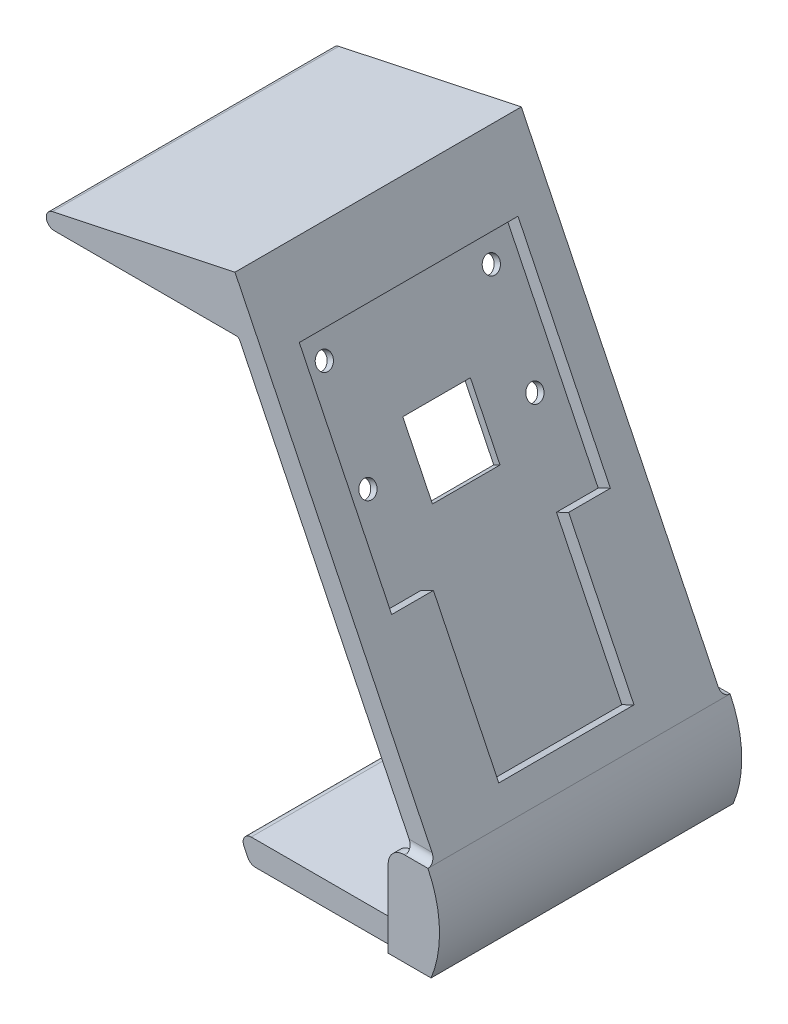
SolidWorks part; units mm, degrees
ref_plane "Front Plane" through (0, 0, 0) normal (0, 0, 1) x (1, 0, 0)
ref_plane "Top Plane" through (0, 0, 0) normal (0, 1, 0) x (1, 0, 0)
ref_plane "Right Plane" through (0, 0, 0) normal (1, 0, 0) x (0, 0, -1)
sketch "Sketch2" plane through (0, 0, 0) normal (0, 0, 1) x (1, 0, 0)
  line L0 (0, 0) -> (-25.1844, 51.6357)
  line L1 (0, 0) -> (-52.1043, 0) construction
  line L2 (0, 0) -> (0, -2)
  line L3 (0, -2) -> (-23.62, -2)
  line L6 (-25.1844, 51.6357) -> (-48.3844, 51.6357)
  line L7 (-48.5923, 53.6139) -> (-25.6548, 58.4894)
  line L8 (-25.6548, 58.4894) -> (-0.3927, 6.6946)
  line L10 (-24.04, -4.4528) -> (-24.5278, -3.4528)
  line L11 (0, -5.0472) -> (-23.13, -5.0472)
  arc A0 (-48.5923, 53.6139) -> (-48.3844, 51.6357) centre (-48.3844, 52.6357) ccw
  arc A1 (-23.62, -2) -> (-24.5278, -3.4528) centre (-23.62, -3.01) ccw
  arc A3 (-24.04, -4.4528) -> (-23.13, -5.0472) centre (-23.0873, -3.9881) ccw
  arc A4 (-0.3927, 6.6946) -> (0, -5.0472) centre (-13.3306, 0.3843) cw
  point P17 (-13.3306, 0.3843)
  dimension "D6" = 1
  dimension "D12" = 1.01
  dimension "D8" = 1.06
  dimension "D1" = 64
  dimension "D2" = 57.45
  dimension "D3" = 23.2
  dimension "D4" = 23.45
  dimension "D5" = 12
  dimension "D7" = 23.62
  dimension "D9" = 2
  dimension "D10" = 1
  dimension "D11" = 64
  dimension "D14" = 23.13
extrude "Boss-Extrude1" add sketch "Sketch2" along normal blind 36 contours L6 A0 L7 L8 A4 L11 A3 L10 A1 L3 L2 L0
sketch "Sketch4" plane through (2.3204, 1.1317, 0) normal (0.8988, 0.4384, 0) x (0, 0, -1)
  line L0 (-18, 53.8162) -> (-18, 29.8162) construction
  line L1 (-30.5, 29.8162) -> (-5.5, 29.8162)
  line L2 (-30.5, 29.8162) -> (-30.5, 53.8162)
  line L3 (-30.5, 53.8162) -> (-5.5, 53.8162)
  line L4 (-5.5, 29.8162) -> (-5.5, 53.8162)
  line L5 (-28.5, 53.8162) -> (-28.5, 29.8162) construction
  line L6 (-7.5, 29.8162) -> (-7.5, 53.8162) construction
  line L7 (-30.5, 51.8162) -> (-5.5, 51.8162) construction
  line L8 (-30.5, 39.3162) -> (-5.5, 39.3162) construction
  line L9 (-36, 63.8162) -> (0, 63.8162) construction
  line L10 (-36, 63.8162) -> (-36, 6.1892) construction
  line L11 (-31.75, 28.5662) -> (-31.75, 55.0662)
  line L12 (-31.75, 55.0662) -> (-4.25, 55.0662)
  line L13 (-13.75, 35.0662) -> (-22.25, 35.0662)
  line L14 (-13.75, 35.0662) -> (-13.75, 43.5662)
  line L15 (-13.75, 43.5662) -> (-22.25, 43.5662)
  line L16 (-22.25, 35.0662) -> (-22.25, 43.5662)
  line L17 (-13.75, 35.0662) -> (-22.25, 43.5662) construction
  line L18 (-13.75, 43.5662) -> (-22.25, 35.0662) construction
  line L19 (-4.25, 28.5662) -> (-4.25, 55.0662)
  line L20 (-31.75, 28.5662) -> (-4.25, 28.5662)
  circle A0 centre (-28.5, 51.8162) radius 1.05
  circle A1 centre (-28.5, 39.3162) radius 1.05
  circle A2 centre (-7.5, 51.8162) radius 1.05
  circle A3 centre (-7.5, 39.3162) radius 1.05
  point P20 (-18, 39.3162)
  dimension "D10" = 2.1
  dimension "D1" = 25
  dimension "D2" = 24
  dimension "D3" = 2
  dimension "D4" = 12.5
  dimension "D5" = 21
  dimension "D6" = 2
  dimension "D7" = 10
  dimension "D8" = 5.5
  dimension "D9" = 8.5
  dimension "D11" = 1.25
extrude "Cut-Extrude1" cut sketch "Sketch4" against normal through all contours A0 | A2 | A3 | A1 | L16 L15 L14 L13
extrude "Cut-Extrude2" cut sketch "Sketch4<3>" against normal blind 1.7 contours L11 L20 L19 L12 L4 L1 L2 L3 | L1 L4 L3 L2 A3 A2 A1 A0 L13 L16 L15 L14 region at (-16.0106, 38.7159, 30.1534) region at (-16.0106, 38.7159, 31.3681)
sketch "Sketch4<3>" plane through (2.3204, 1.1317, 0) normal (0.8988, 0.4384, 0) x (0, 0, -1) same geometry as "Sketch4"
sketch "Sketch5" plane through (2.3204, 1.1317, 0) normal (0.8988, 0.4384, 0) x (0, 0, -1)
  line L0 (-30.5, 29.8162) -> (-5.5, 29.8162) construction
  line L1 (-30.5, 29.8162) -> (-5.5, 29.8162)
  line L2 (-18, 53.8162) -> (-18, 29.8162) construction
  line L3 (-26.5, 29.8162) -> (-9.5, 29.8162)
  line L4 (-26.5, 29.8162) -> (-26.5, 9.8162)
  line L5 (-26.5, 9.8162) -> (-9.5, 9.8162)
  line L6 (-9.5, 29.8162) -> (-9.5, 9.8162)
  dimension "D1" = 20
  dimension "D2" = 17
  dimension "D3" = 8.5
extrude "Cut-Extrude3" cut sketch "Sketch5" against normal blind 1.7 contours L4 L5 L6 L3
fillet "Fillet1" radius 0.5 2 edges at (-25.1844, 51.6357, 18) (0, 0, 18)
sketch "Sketch6" plane through (0, 0, 36) normal (0, 0, 1) x (1, 0, 0)
  line L0 (-0.3927, 6.6946) -> (-3.3927, 6.6946)
  line L1 (-5.3927, 4.6946) -> (-5.3927, -5.0472)
  line L2 (0, -5.0472) -> (-23.13, -5.0472) construction
  line L3 (-5.3927, -5.0472) -> (0, -5.0472)
  arc A0 (0, -5.0472) -> (-0.3927, 6.6946) centre (-13.3306, 0.3843) ccw construction
  arc A1 (0, -5.0472) -> (-0.3927, 6.6946) centre (-13.3306, 0.3843) ccw
  arc A2 (-3.3927, 6.6946) -> (-5.3927, 4.6946) centre (-3.3927, 4.6946) ccw
  point P9 (-5.3927, 6.6946)
  dimension "D2" = 2
  dimension "D1" = 5
extrude "Boss-Extrude2" add sketch "Sketch6" along normal blind 1
fillet "Fillet2" radius 1 2 edges at (-5.3927, -3.5236, 36) (-1.829, 6.6946, 36)
ref_plane "Plane1" through (0, 0, 18) normal (0, 0, -1) x (-1, 0, 0)
mirror "Mirror3" about plane through (0, 0, 18) normal (0, 0, -1) of "Boss-Extrude2"
fillet "Fillet3" radius 1 2 edges at (-5.3927, -3.5236, 0) (-1.829, 6.6946, 0)
